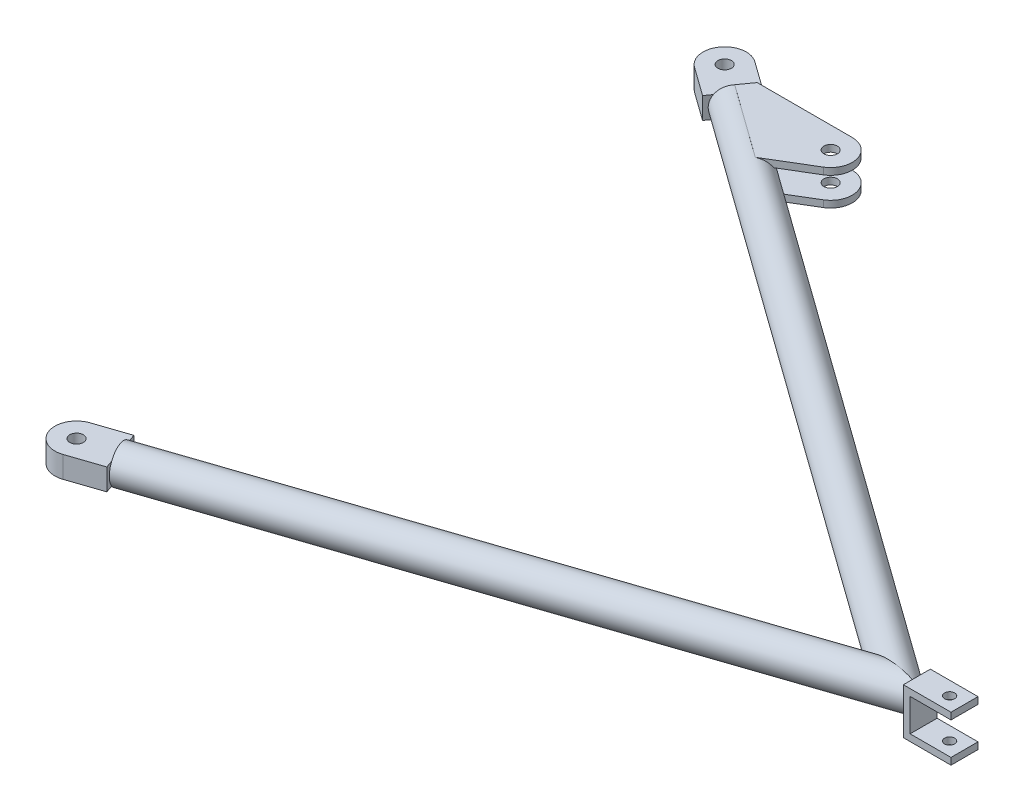
SolidWorks part; units mm, degrees
ref_plane "Front Plane" through (0, 0, 0) normal (0, 0, 1) x (1, 0, 0)
ref_plane "Top Plane" through (0, 0, 0) normal (0, 1, 0) x (1, 0, 0)
ref_plane "Right Plane" through (0, 0, 0) normal (1, 0, 0) x (0, 0, -1)
sketch "Sketch1" plane through (0, 0, 0) normal (0, 1, 0) x (1, 0, 0)
  line L0 (-288.83, -97.3667) -> (0, 0)
  line L1 (0, 0) -> (-288.83, 207.4333)
  line L2 (-288.83, 207.4333) -> (-288.83, -97.3667) construction
  dimension "D1" = 304.8
  dimension "D2" = 355.6
  dimension "D3" = 304.8
ref_plane "Plane1" through (-288.83, 0, 97.3667) normal (0.9476, 0, -0.3194) x (-0.3194, 0, -0.9476)
sketch "Sketch2" plane through (-288.83, 0, 97.3667) normal (0.9476, 0, -0.3194) x (-0.3194, 0, -0.9476)
  circle A0 centre (0, 0) radius 8.255
  dimension "D1" = 16.51
sweep "Sweep1" add profiles "Sketch2" path "Sketch1"
sketch "Sketch3" plane through (0, 0, 0) normal (0, 0, 1) x (1, 0, 0)
  line L0 (33.9318, 10.795) -> (11.5358, 10.795)
  line L1 (11.5358, 10.795) -> (11.5358, -10.795)
  line L2 (11.5358, -10.795) -> (33.9318, -10.795)
  line L3 (33.9318, -10.795) -> (33.9318, -7.62)
  line L4 (33.9318, -7.62) -> (14.7108, -7.62)
  line L5 (14.7108, -7.62) -> (14.7108, 7.62)
  line L6 (14.7108, 7.62) -> (33.9318, 7.62)
  line L7 (33.9318, 7.62) -> (33.9318, 10.795)
  line L8 (17.8858, 0) -> (-17.8858, 0) construction
  ellipse E0 centre (0, 0) end of major axis (17.8858, 0) minor radius 8.255 construction
  ellipse E1 centre (0, 0) end of major axis (17.8858, 0) minor radius 8.255 construction
  point P21 (11.5358, 0)
  dimension "D1" = 3.175
  dimension "D2" = 15.24
  dimension "D3" = 3.175
  dimension "D4" = 6.35
extrude "Boss-Extrude1" add sketch "Sketch3" along normal blind 8.89 and the other way blind 3.81
sketch "Sketch4" plane through (-288.83, 0, 97.3667) normal (-0.9476, 0, 0.3194) x (0.3194, 0, 0.9476)
  line L1 (-10.16, 5.08) -> (10.16, 5.08)
  line L2 (-10.16, 5.08) -> (-10.16, -5.08)
  line L3 (-10.16, -5.08) -> (10.16, -5.08)
  line L4 (10.16, 5.08) -> (10.16, -5.08)
  line L5 (-10.16, 5.08) -> (10.16, -5.08) construction
  line L6 (-10.16, -5.08) -> (10.16, 5.08) construction
  circle A1 centre (0, 0) radius 8.255
  circle A2 centre (0, 0) radius 8.255 construction
  dimension "D2" = 20.32
  dimension "D3" = 10.16
  dimension "D1" = 0
extrude "Boss-Extrude2" add sketch "Sketch4" along normal blind 10.16 and the other way blind 16.256
sketch "Sketch5" plane through (-288.83, 0, -207.4333) normal (-0.8122, 0, -0.5833) x (-0.5833, 0, 0.8122)
  line L1 (-10.16, 5.08) -> (10.16, 5.08)
  line L2 (-10.16, 5.08) -> (-10.16, -5.08)
  line L3 (-10.16, -5.08) -> (10.16, -5.08)
  line L4 (10.16, 5.08) -> (10.16, -5.08)
  line L5 (-10.16, 5.08) -> (10.16, -5.08) construction
  line L6 (-10.16, -5.08) -> (10.16, 5.08) construction
  point P0 (0, 0)
  dimension "D1" = 20.32
  dimension "D2" = 10.16
extrude "Boss-Extrude3" add sketch "Sketch5" along normal blind 10.16 and the other way blind 16.51
sketch "Sketch6" plane through (0, 5.08, 0) normal (0, 1, 0) x (1, 0, 0)
  line L0 (-269.4934, 206.0548) -> (-291.1556, 221.6123) construction
  line L1 (-281.3467, 189.5502) -> (-303.009, 205.1077) construction
  line L2 (-303.009, 205.1077) -> (-291.1556, 221.6123) construction
  line L3 (-294.7567, 199.181) -> (-303.009, 205.1077)
  line L4 (-303.009, 205.1077) -> (-297.0823, 213.36)
  arc A0 (-297.0823, 213.36) -> (-294.7567, 199.181) centre (-288.83, 207.4333) ccw
extrude "Cut-Extrude1" cut sketch "Sketch6" against normal through all
ref_plane "Plane2" through (0, 0, 0) normal (-0.5833, 0, 0.8122) x (0.8122, 0, 0.5833)
ref_plane "Plane3" through (0, 0, 0) normal (0.3194, 0, 0.9476) x (0.9476, 0, -0.3194)
mirror "Mirror1" about plane through (0, 0, 0) normal (-0.5833, 0, 0.8122) of "Cut-Extrude1"
sketch "Sketch7" plane through (0, 5.08, 0) normal (0, 1, 0) x (1, 0, 0)
  line L0 (-270.1802, -101.8014) -> (-295.2121, -110.2399) construction
  line L1 (-276.6713, -82.5461) -> (-301.7032, -90.9846) construction
  line L2 (-295.2121, -110.2399) -> (-301.7032, -90.9846) construction
  line L3 (-285.5845, -106.9943) -> (-295.2121, -110.2399)
  line L4 (-295.2121, -110.2399) -> (-298.4577, -100.6122)
  arc A0 (-285.5845, -106.9943) -> (-298.4577, -100.6122) centre (-288.83, -97.3667) cw
extrude "Cut-Extrude2" cut sketch "Sketch7" against normal through all
mirror "Mirror2" about plane through (0, 0, 0) normal (0.3194, 0, 0.9476) of "Cut-Extrude2"
sketch "Sketch8" plane through (-288.83, 0, 97.3667) normal (-0.9476, 0, 0.3194) x (0.3194, 0, 0.9476)
  line L0 (6.5068, -5.08) -> (-6.5068, -5.08) construction
  line L1 (-6.5068, 5.08) -> (6.5068, 5.08) construction
  line L2 (6.5068, -5.08) -> (-6.5068, -5.08)
  line L3 (-6.5068, 5.08) -> (6.5068, 5.08)
  arc A0 (-6.5068, -5.08) -> (6.5068, -5.08) centre (0, 0) ccw construction
  arc A1 (6.5068, 5.08) -> (-6.5068, 5.08) centre (0, 0) ccw construction
  arc A2 (-6.5068, -5.08) -> (6.5068, -5.08) centre (0, 0) ccw
  arc A3 (6.5068, 5.08) -> (-6.5068, 5.08) centre (0, 0) ccw
extrude "Cut-Extrude3" cut sketch "Sketch8" against normal up to surface (16.256 mm away) up to face at (-270.6241, 0, 100.4847)
sketch "Sketch9" plane through (-288.83, 0, -207.4333) normal (-0.8122, 0, -0.5833) x (-0.5833, 0, 0.8122)
  line L0 (6.5068, -5.08) -> (-6.5068, -5.08) construction
  line L1 (-6.5068, 5.08) -> (6.5068, 5.08) construction
  line L2 (6.5068, -5.08) -> (-6.5068, -5.08)
  line L3 (-6.5068, 5.08) -> (6.5068, 5.08)
  arc A0 (-6.5068, -5.08) -> (6.5068, -5.08) centre (0, 0) ccw construction
  arc A1 (6.5068, 5.08) -> (-6.5068, 5.08) centre (0, 0) ccw construction
  arc A2 (-6.5068, -5.08) -> (6.5068, -5.08) centre (0, 0) ccw
  arc A3 (6.5068, 5.08) -> (-6.5068, 5.08) centre (0, 0) ccw
extrude "Cut-Extrude4" cut sketch "Sketch9" against normal up to surface (16.51 mm away) up to face at (-280.5361, 0, -190.6788)
sketch "Sketch10" plane through (0, 5.08, 0) normal (0, 1, 0) x (1, 0, 0)
  point P0 (-288.83, 207.4333)
  point P1 (-288.83, -97.3667)
hole_wizard "E (0.25) Diameter Hole1" positions "3DSketch1" profile "Sketch11" hole size "E" standard "ANSI Inch"
sketch3d "3DSketch1"
  point P0 (-288.83, 5.08, -207.4333)
  point P3 (-288.83, 5.08, 97.3667)
sketch "Sketch11" plane through (-288.83, 5.08, -207.4333) normal (1, 0, 0) x (0, 0, 1)
  line L0 (0, 0) -> (0, 20.9577)
  line L1 (0, 20.9577) -> (3.175, 19.05)
  line L2 (3.175, 19.05) -> (3.175, 0)
  line L5 (3.175, 0) -> (0, 0)
  line L10 (0, 20.9577) -> (-3.175, 19.05) construction
  line L11 (0, -6.35) -> (0, 107.95) construction
  dimension "Hole Dia." = 6.35
  dimension "Hole Depth" = 19.05
  dimension "Drill Angle" = 118
hole_wizard "3/16 (0.1875) Diameter Hole1" positions "Sketch12" profile "Sketch13" hole size "3/16" standard "ANSI Inch" end condition through all
sketch "Sketch12" plane through (0, 10.795, 0) normal (0, 1, 0) x (1, 0, 0)
  point P0 (26.9335, -2.54)
sketch "Sketch13" plane through (26.9335, 10.795, 2.54) normal (1, 0, 0) x (0, 0, 1)
  line L0 (0, 0) -> (0, 21.59)
  line L1 (0, 21.59) -> (2.3812, 21.59)
  line L2 (2.3812, 21.59) -> (2.3812, 0)
  line L5 (2.3812, 0) -> (0, 0)
  line L11 (0, -6.35) -> (0, 107.95) construction
  dimension "Thru Hole Dia." = 4.7625
  dimension "Thru Hole Depth" = 21.59
sketch "Sketch14" plane through (0, 0, 8.89) normal (0, 0, 1) x (1, 0, 0)
  line L1 (14.7108, 4.6953) -> (14.7108, -4.6953)
  line L2 (14.7108, 4.6953) -> (14.7108, -4.6953)
  ellipse E1 centre (0, 0) end of major axis (17.8858, 0) minor radius 8.255 (14.7108, -4.6953) -> (14.7108, 4.6953) ccw
  ellipse E2 centre (0, 0) end of major axis (17.8858, 0) minor radius 8.255 (14.7108, -4.6953) -> (14.7108, 4.6953) ccw
  dimension "D1" = 0
extrude "Cut-Extrude5" cut sketch "Sketch14" against normal through all
ref_point "Point1"
ref_point "Point2"
sketch3d "3DSketch2"
  line L0 (26.9335, 10.795, 2.54) -> (26.9335, -10.795, 2.54)
  circle A0 centre (26.9335, 10.795, 2.54) radius 2.3812 construction
  circle A1 centre (26.9335, 10.795, 2.54) radius 2.3812
  circle A2 centre (26.9335, -10.795, 2.54) radius 2.3812 construction
  circle A3 centre (26.9335, -10.795, 2.54) radius 2.3812
  point P2 (26.9335, 13.1762, 2.54)
  point P4 (26.9335, 13.1762, 2.54)
  point P7 (26.9335, -8.4138, 2.54)
  point P9 (26.9335, -8.4138, 2.54)
  point P10 (26.9335, 0, 2.54)
  point P11 (26.9335, 0, 2.54)
ref_point "Point3"
sketch "Sketch15" plane through (0, 0, 0) normal (0, 1, 0) x (1, 0, 0)
  line L0 (-270.6046, 204.5075) -> (-225.9006, 204.5075)
  line L1 (-233.5551, 177.8991) -> (-220.6698, 185.6375)
  line L3 (11.5358, 1.8785) -> (-270.6046, 204.5075) construction
  line L4 (-233.5551, 177.8991) -> (-240.632, 173.649)
  line L5 (-240.632, 173.649) -> (-283.5993, 204.5075)
  line L6 (-270.6046, 204.5075) -> (-283.5993, 204.5075)
  line L7 (-275.0264, 198.3506) -> (-270.6046, 204.5075)
  line L8 (-271.6244, 203.0875) -> (-279.2157, 192.5175) construction
  arc A0 (-225.9006, 204.5075) -> (-220.6698, 185.6375) centre (-225.9006, 194.3475) cw
  circle A2 centre (-225.9006, 194.3475) radius 3.175
  dimension "D2" = 10.16
  dimension "D3" = 6.35
  dimension "D1" = 44.704
  dimension "D4" = 8.255
extrude "Boss-Extrude4" add sketch "Sketch15" against normal blind 3.175 from offset 8.255 separate body contours A0 L0 L7 L5 L4 L1 A2 region at (-242.9747, 0, -192.8822)
sketch "Sketch16" plane through (0, 0, 0) normal (0, 1, 0) x (1, 0, 0)
  line L0 (-275.0264, 198.3506) -> (-270.6046, 204.5075) construction
  line L1 (-275.0264, 198.3506) -> (-270.6046, 204.5075)
  line L5 (-225.9006, 204.5075) -> (-270.6046, 204.5075)
  line L6 (-233.5551, 177.8991) -> (-220.6698, 185.6375)
  line L7 (-240.632, 173.649) -> (-233.5551, 177.8991)
  line L8 (-283.5993, 204.5075) -> (-240.632, 173.649)
  line L9 (-270.6046, 204.5075) -> (-283.5993, 204.5075)
  line L10 (-225.9006, 204.5075) -> (-270.6046, 204.5075)
  line L11 (-233.5551, 177.8991) -> (-220.6698, 185.6375)
  line L12 (-240.632, 173.649) -> (-233.5551, 177.8991)
  line L13 (-283.5993, 204.5075) -> (-240.632, 173.649)
  line L14 (-270.6046, 204.5075) -> (-283.5993, 204.5075)
  circle A1 centre (-225.9006, 194.3475) radius 3.175
  circle A2 centre (-225.9006, 194.3475) radius 3.175
  arc A3 (-220.6698, 185.6375) -> (-225.9006, 204.5075) centre (-225.9006, 194.3475) ccw
  arc A4 (-220.6698, 185.6375) -> (-225.9006, 204.5075) centre (-225.9006, 194.3475) ccw
  dimension "D1" = 0
  dimension "D2" = 0
extrude "Boss-Extrude6" add sketch "Sketch16" along normal blind 3.175 from offset 8.255 separate body contours L11 A4 L10 L1 L13 L12 A2 region at (-242.9747, 0, -192.8822) offset against normal yes
sketch3d "3DSketch3"
  line L0 (-225.9006, 8.255, -194.3475) -> (-225.9006, -8.255, -194.3475)
  circle A0 centre (-225.9006, 8.255, -194.3475) radius 3.175 construction
  circle A1 centre (-225.9006, 8.255, -194.3475) radius 3.175
  circle A2 centre (-225.9006, -8.255, -194.3475) radius 3.175 construction
  circle A3 centre (-225.9006, -8.255, -194.3475) radius 3.175
  point P2 (-225.9006, 11.43, -194.3475)
  point P4 (-225.9006, 11.43, -194.3475)
  point P7 (-225.9006, -5.08, -194.3475)
  point P9 (-225.9006, -5.08, -194.3475)
  point P10 (-225.9006, 0, -194.3475)
ref_point "Point4"
